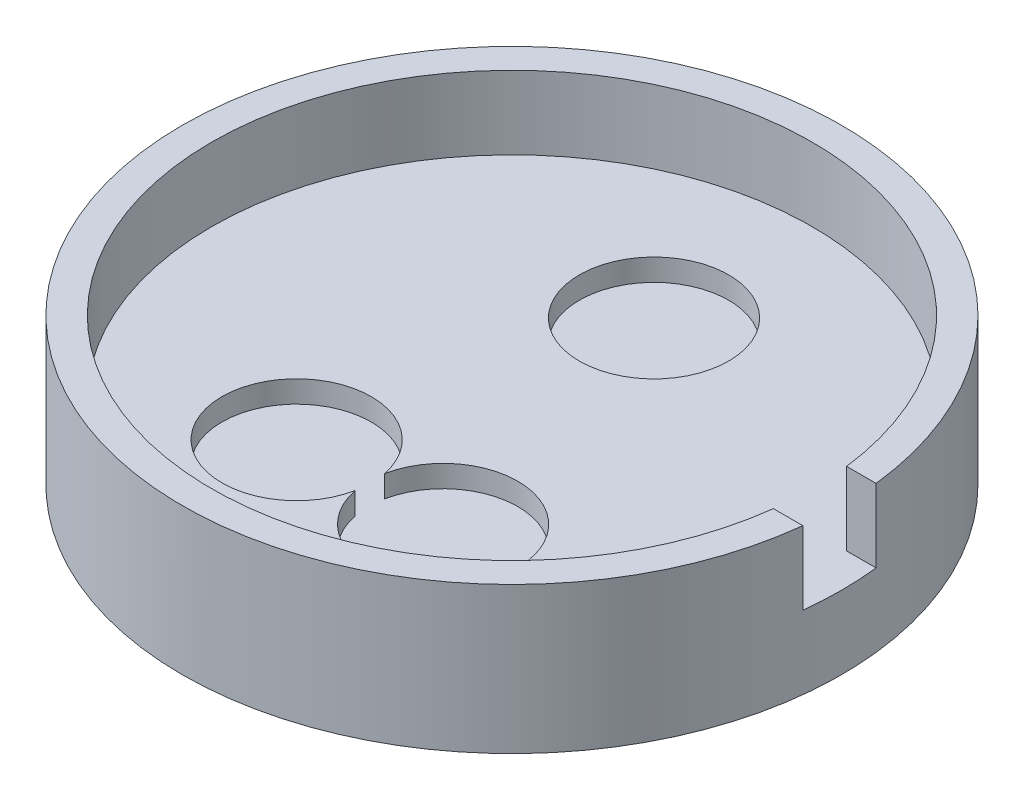
SolidWorks part; units mm, degrees
ref_plane "前视基准面" through (0, 0, 0) normal (0, 0, 1) x (1, 0, 0)
ref_plane "上视基准面" through (0, 0, 0) normal (0, 1, 0) x (1, 0, 0)
ref_plane "右视基准面" through (0, 0, 0) normal (1, 0, 0) x (0, 0, -1)
other "Configuration Table"
sketch "草图1" plane through (0, 0, 0) normal (0, 1, 0) x (1, 0, 0)
  circle A0 centre (0, 0) radius 20.5
  circle A1 centre (0, 0) radius 22.5
  point P8 (0, 0)
  point P9 (0, 0)
  point P10 (0, 0)
  dimension "D1" = 41
  dimension "D2" = 2
extrude "凸台-拉伸1" add sketch "草图1" along normal blind 5
extrude "凸台-拉伸2" add sketch "草图1<4>" against normal blind 5 contours A1
sketch "草图1<4>" plane through (0, 0, 0) normal (0, 1, 0) x (1, 0, 0) same geometry as "草图1"
sketch "草图2" plane through (0, 0, 0) normal (0, 1, 0) x (1, 0, 0)
  line L0 (-5, -9.7) -> (5, -9.7) construction
  line L1 (0, -9.7) -> (0, 0) construction
  line L2 (0, 0) -> (0, 9.7) construction
  circle A0 centre (0, 9.7) radius 5.1
  circle A1 centre (-5, -9.7) radius 5.1
  circle A2 centre (5, -9.7) radius 5.1
  dimension "D1" = 10.2
  dimension "D2" = 10
  dimension "D3" = 9.7
extrude "切除-拉伸1" cut sketch "草图2" against normal blind 1.5 contours A0 | A2 | A1
sketch "草图3" plane through (0, 5, 0) normal (0, 1, 0) x (1, 0, 0)
  line L1 (0, 2.5) -> (30, 2.5)
  line L2 (0, 2.5) -> (0, -2.5)
  line L3 (0, -2.5) -> (30, -2.5)
  line L4 (30, 2.5) -> (30, -2.5)
  dimension "D1" = 5
  dimension "D2" = 30
extrude "切除-拉伸2" cut sketch "草图3" against normal up to surface (5 mm away) up to face at (0, 0, -4.6)
sketch "草图4" plane through (0, -5, 0) normal (0, -1, 0) x (1, 0, 0)
  line L0 (-10, 0) -> (10, 0) construction
  circle A0 centre (-10, 0) radius 0.6
  circle A1 centre (10, 0) radius 0.6
  dimension "D1" = 1.2
  dimension "D2" = 1.2
  dimension "D3" = 20
extrude "切除-拉伸3" cut sketch "草图4" against normal blind 3
